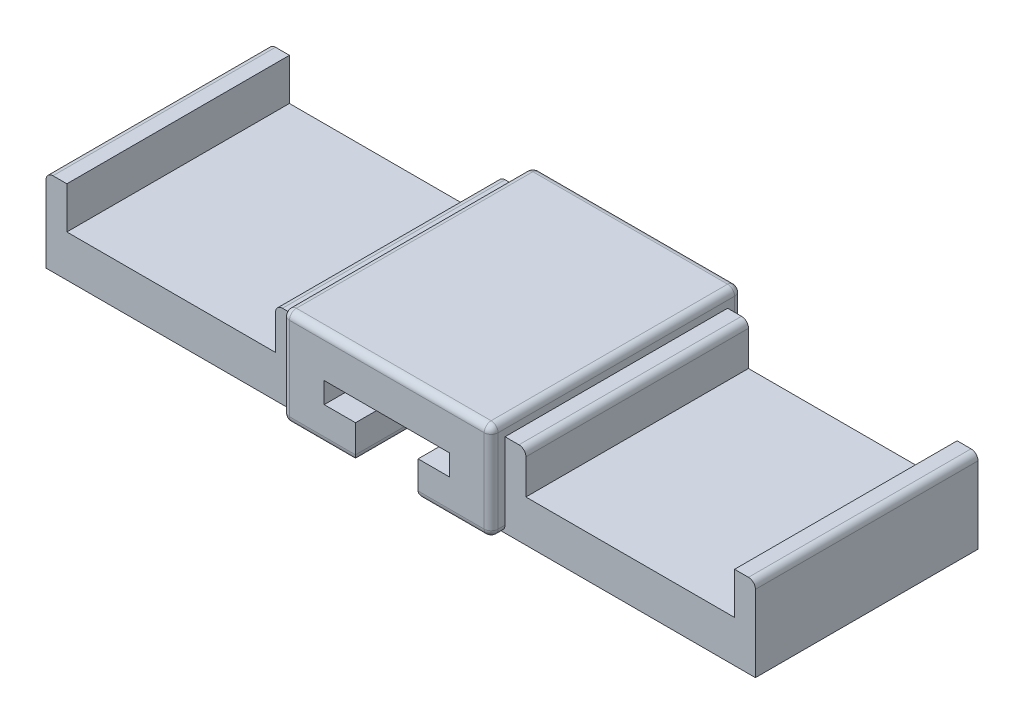
SolidWorks part; units mm, degrees
ref_plane "Front Plane" through (0, 0, 0) normal (0, 0, 1) x (1, 0, 0)
ref_plane "Top Plane" through (0, 0, 0) normal (0, 1, 0) x (1, 0, 0)
ref_plane "Right Plane" through (0, 0, 0) normal (1, 0, 0) x (0, 0, -1)
sketch "Sketch1" plane through (0, 0, 0) normal (0, 1, 0) x (1, 0, 0)
  line L1 (-7.5, -9) -> (7.5, -9)
  line L2 (-7.5, -9) -> (-7.5, 9)
  line L3 (-7.5, 9) -> (7.5, 9)
  line L4 (7.5, -9) -> (7.5, 9)
  line L5 (-7.5, -9) -> (7.5, 9) construction
  line L6 (-7.5, 9) -> (7.5, -9) construction
  point P0 (0, 0)
  dimension "D1" = 18
  dimension "D2" = 15
extrude "Boss-Extrude1" add sketch "Sketch1" along normal blind 7
sketch "Sketch2" plane through (0, 0, 9) normal (0, 0, 1) x (1, 0, 0)
  line L0 (-4.5, 0) -> (4.5, 0)
  line L1 (-7.5, 0) -> (7.5, 0) construction
  line L2 (4.5, 0) -> (4.5, 4)
  line L3 (4.5, 4) -> (-4.5, 4)
  line L4 (-4.5, 4) -> (-4.5, 0)
  line L5 (-4.5, 2.5) -> (4.5, 2.5)
  line L6 (-2.25, 2.5) -> (-2.25, 0)
  line L7 (0, 0) -> (0, 7) construction
  line L8 (-7.5, 7) -> (7.5, 7) construction
  line L9 (2.25, 2.5) -> (2.25, 0)
  line L10 (-0.6, 0) -> (-0.6, 5)
  line L11 (-0.6, 5) -> (0.6, 5)
  line L12 (0.6, 5) -> (0.6, 0)
  line L13 (1.1, 2.5) -> (1.1, 0)
  line L14 (-1.1, 2.5) -> (-1.1, 0)
  point P6 (0, 0)
  dimension "D1" = 4
  dimension "D2" = 1.5
  dimension "D3" = 4.5
  dimension "D4" = 1.2
  dimension "0.5" = 0.5
  dimension "D6" = 9
extrude "Cut-Extrude1" cut sketch "Sketch2" against normal blind 16.2 contours L5 L10 L3 L4 | L3 L12 L5 L2 | L5 L7 L3 L10 | L7 L5 L12 L3 | L14 L5 L6 L0 | L5 L14 L4 L10 | L4 L7 L5 L10 | L7 L0 L12 L5 | L13 L5 L12 L0 | L5 L13 L4 L9 region at (-1.675, 1.25, 9) region at (-2.55, 3.25, 9) region at (-0.85, 1.25, 9) region at (-0.3, 1.25, 9) region at (-0.3, 3.25, 9) region at (0.3, 1.25, 9) region at (0.3, 3.25, 9) region at (0.85, 1.25, 9) region at (2.55, 3.25, 9) region at (1.675, 1.25, 9)
sketch "Sketch8" plane through (0, 0, 9) normal (0, 0, 1) x (1, 0, 0)
  line L0 (-1.1, 2.6) -> (-0.6, 2.6)
  line L1 (-0.6, 2.6) -> (-0.6, 0)
  line L2 (-0.6, 0) -> (-1.1, 0)
  line L3 (-1.1, 0) -> (-1.1, 2.6)
  line L4 (0.6, 2.6) -> (1.1, 2.6)
  line L5 (1.1, 2.6) -> (1.1, 0)
  line L6 (1.1, 0) -> (0.6, 0)
  line L7 (0.6, 0) -> (0.6, 2.6)
sketch "Sketch9" plane through (-7.5, 0, 0) normal (-1, 0, 0) x (0, 0, 1)
  line L0 (-8, 0) -> (-8, 6)
  line L1 (9, 0) -> (-9, 0) construction
  line L2 (-8, 6) -> (8, 6)
  line L3 (8, 6) -> (8, 0)
  line L4 (-9, 0) -> (9, 0) construction
  line L5 (8, 0) -> (-8, 0)
  line L6 (-0.3093, 0) -> (0, 0) construction
  line L7 (0, 0) -> (0, 6) construction
  dimension "D1" = 16
  dimension "D2" = 6
extrude "Boss-Extrude2" add sketch "Sketch9" along normal blind 18
sketch "Sketch12" plane through (0, 0, 8) normal (0, 0, 1) x (1, 0, 0)
  line L0 (-16.5, 0) -> (-16.5, 6) construction
  line L1 (-25.5, 0) -> (-7.5, 0) construction
  line L2 (-25.5, 6) -> (-7.5, 6) construction
  dimension "D1" = 16.5
sketch "Sketch13" plane through (7.5, 0, 0) normal (1, 0, 0) x (0, 0, -1)
  line L0 (-8, 0) -> (-8, 6)
  line L1 (-8, 0) -> (-8, 6) construction
  line L2 (-8, 6) -> (8, 6)
  line L3 (8, 6) -> (8, 0)
  line L4 (9, 0) -> (-9, 0) construction
  line L5 (8, 0) -> (-8, 0)
  line L6 (0, 0) -> (0, 7) construction
  line L7 (-9, 0) -> (9, 0) construction
  line L8 (-9, 7) -> (9, 7) construction
  dimension "D2" = 6
extrude "Boss-Extrude3" add sketch "Sketch13" along normal blind 18
sketch "Sketch14" plane through (0, 0, 9) normal (0, 0, 1) x (1, 0, 0)
  line L0 (0, 0) -> (0, 7) construction
  line L1 (-7.5, 7) -> (7.5, 7) construction
  line L3 (25.5, 0) -> (7.5, 0) construction
  line L7 (16.5, 0) -> (16.5, 0.2814) construction
  line L12 (16.5, 0) -> (16.5, 6) construction
  line L13 (25.5, 6) -> (7.5, 6) construction
  line L17 (9, 6) -> (9, 3)
  line L18 (9, 3) -> (24, 3)
  line L19 (24, 3) -> (24, 6)
  line L20 (24, 6) -> (9, 6)
  line L23 (-24, 3) -> (-24, 6)
  line L24 (-9, 3) -> (-24, 3)
  line L25 (-9, 6) -> (-9, 3)
  line L30 (-24, 6) -> (-9, 6)
  dimension "D1" = 15
  dimension "D2" = 3
extrude "Cut-Extrude5" cut sketch "Sketch14" against normal blind 32.55
fillet "Fillet1" radius 0.5 21 edges at (0, 0, -9) (7.5, 0, -8.5) (-7.5, 0, -8.5) (-7.5, 0, 8.5) (7.5, 0, 8.5) (7.5, 7, 0) (25.5, 6, 0) (-25.5, 6, 0) (-7.5, 7, 0) (-7.5, 3.5, 9) (7.5, 3.5, 9) (4.875, 0, 9) (2.25, 0, 0.9) (-2.25, 0, 0.9) (-4.875, 0, 9) (0, 7, 9) (0, 7, -9) (7.5, 3.5, -9) (-7.5, 3.5, -9) (-9, 6, 0) (9, 6, 0)
